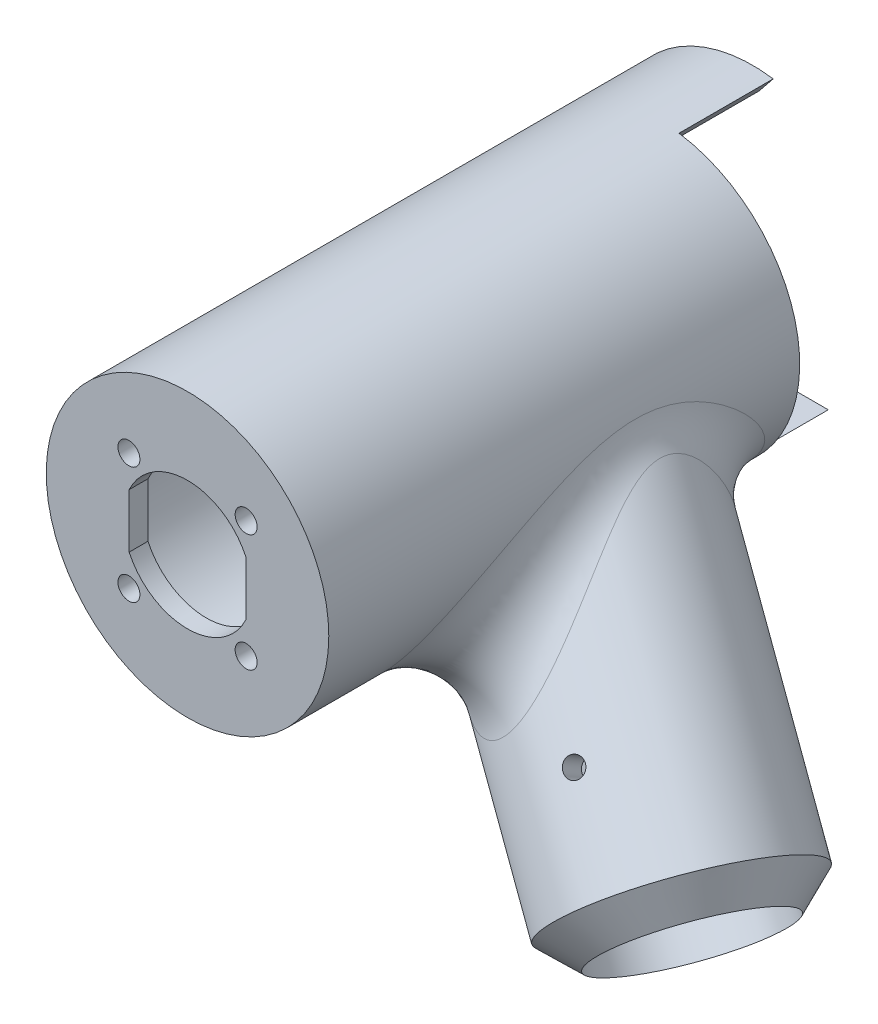
SolidWorks part; units mm, degrees
material "ABS"
ref_plane "Front Plane" through (0, 0, 0) normal (0, 0, 1) x (1, 0, 0)
ref_plane "Top Plane" through (0, 0, 0) normal (0, 1, 0) x (1, 0, 0)
ref_plane "Right Plane" through (0, 0, 0) normal (1, 0, 0) x (0, 0, -1)
sketch "Sketch1" plane through (0, 0, 0) normal (0, 0, 1) x (1, 0, 0)
  circle A0 centre (0, 0) radius 22.5
  dimension "D1" = 45
extrude "Boss-Extrude1" add sketch "Sketch1" along normal blind 90
sketch "Sketch2" plane through (0, 0, 0) normal (0, 0, -1) x (-1, 0, 0)
  circle A0 centre (0, 0) radius 16.2
  circle A1 centre (0, 0) radius 22.5 construction
  dimension "D1" = 6.3
extrude "Cut-Extrude1" cut sketch "Sketch2" against normal offset from surface (87 mm away) 3 up to face at (22.5, 0, 90)
sketch "Sketch3" plane through (0, 0, 0) normal (1, 0, 0) x (0, 0, -1)
  line L1 (15, -19) -> (-15, -19)
  line L2 (15, -19) -> (15, 19)
  line L3 (15, 19) -> (-15, 19)
  line L4 (-15, -19) -> (-15, 19)
  line L5 (15, -19) -> (-15, 19) construction
  line L6 (15, 19) -> (-15, -19) construction
  point P0 (0, 0)
  dimension "D1" = 15
  dimension "D2" = 38
extrude "Cut-Extrude2" cut sketch "Sketch3" along normal blind 33
sketch "Sketch4" plane through (0, 0, 0) normal (1, 0, 0) x (0, 0, -1)
  line L0 (0, 0) -> (-40, 0) construction
  line L1 (0, -22.5) -> (0, 22.5) construction
  line L2 (-10, 15) -> (-60, 15)
  line L3 (-10, 15) -> (-10, -15)
  line L4 (-10, -15) -> (-60, -15)
  line L5 (-60, 15) -> (-60, -15)
  line L6 (-10, 15) -> (-60, -15) construction
  line L7 (-10, -15) -> (-60, 15) construction
  point P2 (-35, 0)
  dimension "D1" = 50
  dimension "D2" = 10
  dimension "D3" = 30
ref_plane "Plane2" through (0, 0, 35) normal (0, 0, -1) x (-1, 0, 0)
sketch3d "3DSketch1"
  line L0 (0, 0, 35) -> (120, -120, 90)
sketch "Sketch5" plane through (0, 0, 35) normal (0, 0, -1) x (-1, 0, 0)
  line L0 (0, 0) -> (-54.3806, -54.3806)
  line L1 (0, 15) -> (0, -15) construction
  dimension "D1" = 45
ref_plane "Plane3" through (0, 0, 35) normal (0.6727, -0.6727, 0.3083) x (0.218, -0.218, -0.9513)
sketch "Sketch6" plane through (0, 0, 35) normal (0.6727, -0.6727, 0.3083) x (0.218, -0.218, -0.9513)
  circle A0 centre (0, 0) radius 17.5
  dimension "D1" = 35
extrude "Boss-Extrude2" add sketch "Sketch6" along normal blind 70
sketch "Sketch7" plane through (54.3448, -54.3448, 24.908) normal (0.6727, -0.6727, 0.3083) x (0.218, -0.218, -0.9513)
  circle A0 centre (-33.2951, 0) radius 12.9
  dimension "D1" = 25.8
extrude "Cut-Extrude3" cut sketch "Sketch7" against normal blind 50
sketch "Sketch8" plane through (0, 0, 0) normal (0, 0, -1) x (-1, 0, 0)
  circle A0 centre (0, 0) radius 19.5
extrude "Cut-Extrude4" cut sketch "Sketch8" against normal blind 61
fillet "Fillet1" radius 10 1 edges at (22.3843, 2.2789, 41.1361)
chamfer "Chamfer1" distance 5 angle 45 1 edges at (59.4607, -34.712, 56.5812)
ref_plane "Plane4" through (12.052, -19, 15) normal (0.7354, 0.6538, -0.178) x (-0.459, 0.2874, -0.8407)
sketch "Sketch9" plane through (12.052, -19, 15) normal (0.7354, 0.6538, -0.178) x (-0.459, 0.2874, -0.8407)
  line L0 (-55.3018, -12.6166) -> (-46.2319, -4.8898) construction
  line L1 (-43.9531, -25.9379) -> (-66.6504, 0.7047) construction
  line L2 (-5.8225, 29.5355) -> (-141.6207, -86.1531) construction
  circle A0 centre (-41.5998, -0.9437) radius 1.5
  dimension "D1" = 3
  dimension "D2" = 18
extrude "Cut-Extrude5" [suppressed] cut sketch "Sketch9" against normal blind 63
sketch "Sketch10" plane through (0, 0, 61) normal (0, 0, -1) x (-1, 0, 0)
  circle A0 centre (0, 0) radius 16.2 construction
  circle A1 centre (0, 0) radius 19.5
  circle A2 centre (0, 0) radius 19.5
  circle A3 centre (0, 0) radius 16.2
  dimension "D1" = 0
extrude "Boss-Extrude4" add sketch "Sketch10" along direction (0, 0, 1) on the side of the normal offset from surface (36 mm away) 25 up to face at (-6.3901, 0, 0)
sketch "Sketch11" plane through (0, 0, 87) normal (0, 0, -1) x (-1, 0, 0)
  line L0 (-9.3, -4.3096) -> (-9.3, 4.3096)
  line L1 (0, -10.25) -> (0, 13.1651) construction
  line L2 (9.3, -4.3096) -> (9.3, 4.3096)
  arc A0 (-9.3, -4.3096) -> (9.3, -4.3096) centre (0, 0) ccw
  arc A1 (9.3, 4.3096) -> (-9.3, 4.3096) centre (0, 0) ccw
  circle A2 centre (0, 13.2) radius 1.75
  circle A3 centre (9.3338, 9.3338) radius 1.75
  circle A4 centre (13.2, 0) radius 1.75
  circle A5 centre (9.3338, -9.3338) radius 1.75
  circle A6 centre (0, -13.2) radius 1.75
  circle A7 centre (-9.3338, -9.3338) radius 1.75
  circle A8 centre (-13.2, 0) radius 1.75
  circle A9 centre (-9.3338, 9.3338) radius 1.75
  dimension "D1" = 20.5
  dimension "D3" = 3.5
  dimension "D2" = 9.3
  dimension "D4" = 13.2
  dimension "D5" = 8
extrude "Cut-Extrude6" cut sketch "Sketch11" against normal blind 20.5 contours A7 | L0 A1 L2 A0 | A5 | A3 | A9 region at (9.3338, -9.3338, 87)
pattern_circular "CirPattern1" [suppressed] count 3 over 360 reverse direction yes of bodies 118
ref_plane "Plane5" through (54.0757, -54.0757, 24.7847) normal (0.6727, -0.6727, 0.3083) x (0.218, -0.218, -0.9513)
sketch "Sketch12" plane through (54.0757, -54.0757, 24.7847) normal (0.6727, -0.6727, 0.3083) x (0.218, -0.218, -0.9513)
  line L0 (-46.1951, 0) -> (-12.0884, 0) construction
  circle A0 centre (-33.2951, 0) radius 12.9 construction
ref_axis "Axis1" through (25.876, -25.876, 46.8598) along (0.6727, -0.6727, 0.3083)
ref_plane "Plane6" through (0, 0, 0) normal (-0.7071, -0.7071, 0) x (-0.7071, 0.7071, 0)
sketch "Sketch14" plane through (0, 0, 0) normal (-0.7071, -0.7071, 0) x (-0.7071, 0.7071, 0)
  line L0 (0, -35) -> (-169.7056, -90) construction
  line L1 (-62.2325, -68.7295) -> (-72.7477, -36.2843) construction
  circle A0 centre (-47.1839, -50.2919) radius 1.5
  dimension "D1" = 3
  dimension "D2" = 20
extrude "Cut-Extrude7" cut sketch "Sketch14" along normal blind 40
pattern_circular "CirPattern2" count 3 over 360 about axis through (13.4532, -13.4532, 41.1661) along (0.6727, -0.6727, 0.3083) of "Cut-Extrude7" reverse direction yes
sketch "Sketch15" plane through (0, 0, 0) normal (0, 0, -1) x (-1, 0, 0)
  line L1 (-4.3875, 19) -> (-12.4484, 19)
  line L2 (-4.3875, 19) -> (-4.3875, 26.4516)
  line L3 (-4.3875, 26.4516) -> (-12.4484, 26.4516)
  line L4 (-12.4484, 19) -> (-12.4484, 26.4516)
extrude "Cut-Extrude8" cut sketch "Sketch15" against normal up to surface (15 mm away) up to face at (14.6099, 0, 15)
chamfer "Chamfer2" distance 5 angle 45 1 edges at (4.3875, 19, 7.5) first distance on face at (4.3875, 20.534, 7.5)
